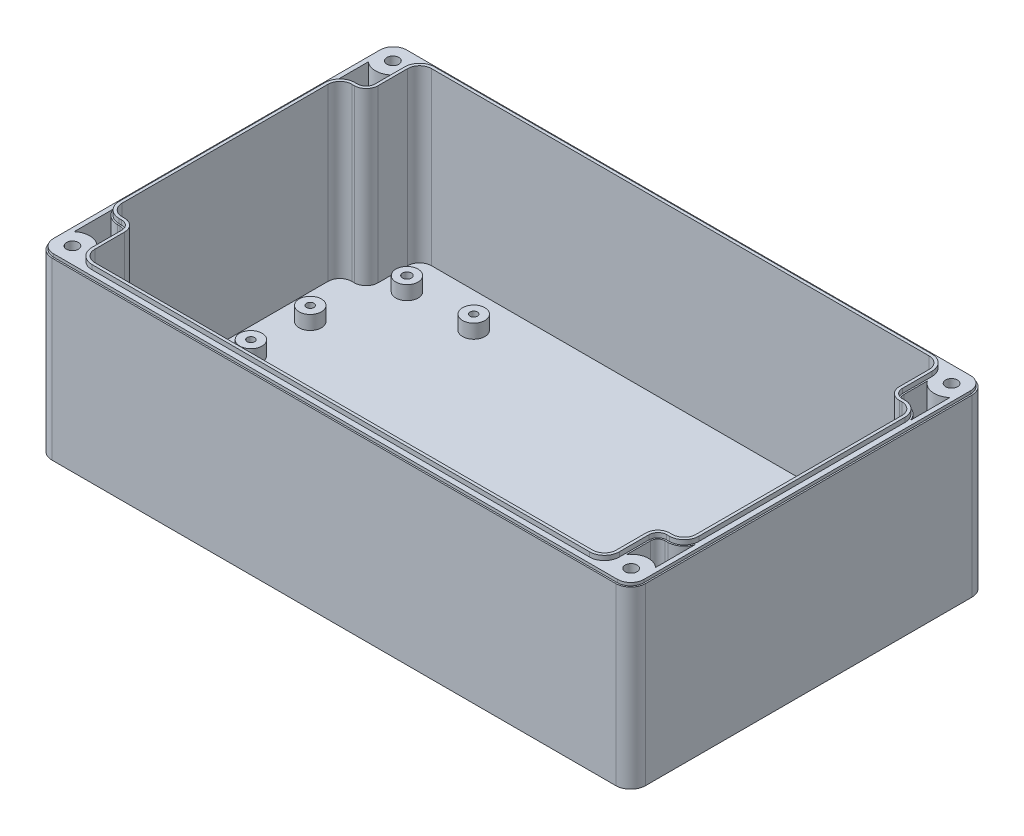
SolidWorks part; units mm, degrees
ref_plane "Front Plane" through (0, 0, 0) normal (0, 0, 1) x (1, 0, 0)
ref_plane "Top Plane" through (0, 0, 0) normal (0, 1, 0) x (1, 0, 0)
ref_plane "Right Plane" through (0, 0, 0) normal (1, 0, 0) x (0, 0, -1)
sketch "Sketch1" plane through (0, 0, 0) normal (0, 1, 0) x (1, 0, 0)
  line L1 (-100, 60) -> (100, 60)
  line L2 (-100, 60) -> (-100, -60)
  line L3 (-100, -60) -> (100, -60)
  line L4 (100, 60) -> (100, -60)
  line L5 (-100, 60) -> (100, -60) construction
  line L6 (-100, -60) -> (100, 60) construction
  point P0 (0, 0)
  dimension "D1" = 200
  dimension "D2" = 120
extrude "Boss-Extrude1" add sketch "Sketch1" along normal blind 60
fillet "Fillet1" radius 5 4 edges at (-100, 30, -60) (100, 30, -60) (100, 30, 60) (-100, 30, 60)
sketch "Sketch2" plane through (0, 60, 0) normal (0, 1, 0) x (1, 0, 0)
  line L0 (0, 60) -> (0, -60) construction
  line L1 (96.7, 56.7) -> (-96.7, 56.7)
  line L2 (96.7, 56.7) -> (96.7, -56.7)
  line L3 (96.7, -56.7) -> (-96.7, -56.7)
  line L4 (-96.7, 56.7) -> (-96.7, -56.7)
  line L5 (96.7, 56.7) -> (-96.7, -56.7) construction
  line L6 (96.7, -56.7) -> (-96.7, 56.7) construction
  line L7 (95, 60) -> (-95, 60) construction
  line L8 (-95, -60) -> (95, -60) construction
  line L9 (-100, 0) -> (99.9439, 0) construction
  line L10 (-100, 55) -> (-100, -55) construction
  line L12 (87.85, -56.7) -> (-87.85, -56.7)
  line L13 (87.85, -56.7) -> (87.85, 56.7)
  line L14 (87.85, 56.7) -> (-87.85, 56.7)
  line L15 (-87.85, -56.7) -> (-87.85, 56.7)
  line L16 (87.85, -56.7) -> (-87.85, 56.7) construction
  line L17 (87.85, 56.7) -> (-87.85, -56.7) construction
  line L18 (96.7, -38.7) -> (-96.7, -38.7)
  line L19 (96.7, -38.7) -> (96.7, 38.7)
  line L20 (96.7, 38.7) -> (-96.7, 38.7)
  line L21 (-96.7, -38.7) -> (-96.7, 38.7)
  line L22 (96.7, -38.7) -> (-96.7, 38.7) construction
  line L23 (96.7, 38.7) -> (-96.7, -38.7) construction
  circle A0 centre (-94.15, 54) radius 2
  circle A2 centre (94.15, 54) radius 2
  circle A3 centre (94.15, -54) radius 2
  circle A4 centre (-94.15, -54) radius 2
  point P0 (0, 0)
  point P18 (0, 0)
  point P19 (0, 0)
  point P30 (0, 0)
  dimension "D5" = 4
  dimension "D1" = 193.4
  dimension "D2" = 113.4
  dimension "D3" = 188.3
  dimension "D4" = 108
  dimension "D6" = 175.7
  dimension "D7" = 77.4
extrude "Cut-Extrude1" cut sketch "Sketch2" against normal offset from surface (56 mm away) 4 contours L20 L13 L1 L15 | L13 L20 L15 L18 | L13 L18 L15 L3 | L15 L20 L4 L18 | L2 L20 L13 L18 | A0 | A4 | A2 | A3 region at (0, 60, -47.7) region at (92.275, 60, 0) region at (0, 60, 0) region at (-92.275, 60, 0) region at (0, 60, 47.7) up to face at (0, 0, 0)
fillet "Fillet2" radius 4 12 edges at (87.85, 32, -56.7) (87.85, 32, -38.7) (96.7, 32, -38.7) (96.7, 32, 38.7) (87.85, 32, 38.7) (87.85, 32, 56.7) (-87.85, 32, 56.7) (-87.85, 32, 38.7) (-96.7, 32, 38.7) (-96.7, 32, -38.7) (-87.85, 32, -56.7) (-87.85, 32, -38.7)
sketch "Sketch3" plane through (0, 60, 0) normal (0, 1, 0) x (1, 0, 0)
  line L1 (83.85, 57.7) -> (-83.85, 57.7)
  line L2 (-88.85, 52.7) -> (-88.85, 42.7)
  line L3 (-91.85, 39.7) -> (-92.7, 39.7)
  line L4 (-97.7, 34.7) -> (-97.7, -34.7)
  line L5 (-92.7, -39.7) -> (-91.85, -39.7)
  line L6 (-88.85, -42.7) -> (-88.85, -52.7)
  line L7 (-83.85, -57.7) -> (83.85, -57.7)
  line L8 (88.85, -52.7) -> (88.85, -42.7)
  line L9 (91.85, -39.7) -> (92.7, -39.7)
  line L10 (97.7, -34.7) -> (97.7, 34.7)
  line L11 (92.7, 39.7) -> (91.85, 39.7)
  line L12 (88.85, 42.7) -> (88.85, 52.7)
  line L13 (87.85, 42.7) -> (87.85, 52.7)
  line L14 (92.7, 38.7) -> (91.85, 38.7)
  line L15 (96.7, -34.7) -> (96.7, 34.7)
  line L16 (91.85, -38.7) -> (92.7, -38.7)
  line L17 (87.85, -52.7) -> (87.85, -42.7)
  line L18 (-83.85, -56.7) -> (83.85, -56.7)
  line L19 (-87.85, -42.7) -> (-87.85, -52.7)
  line L20 (-92.7, -38.7) -> (-91.85, -38.7)
  line L21 (-96.7, 34.7) -> (-96.7, -34.7)
  line L22 (-91.85, 38.7) -> (-92.7, 38.7)
  line L23 (-87.85, 52.7) -> (-87.85, 42.7)
  line L24 (83.85, 56.7) -> (-83.85, 56.7)
  line L25 (87.85, 42.7) -> (87.85, 52.7)
  line L26 (92.7, 38.7) -> (91.85, 38.7)
  line L27 (96.7, -34.7) -> (96.7, 34.7)
  line L28 (91.85, -38.7) -> (92.7, -38.7)
  line L29 (87.85, -52.7) -> (87.85, -42.7)
  line L30 (-83.85, -56.7) -> (83.85, -56.7)
  line L31 (-87.85, -42.7) -> (-87.85, -52.7)
  line L32 (-92.7, -38.7) -> (-91.85, -38.7)
  line L33 (-96.7, 34.7) -> (-96.7, -34.7)
  line L34 (-91.85, 38.7) -> (-92.7, 38.7)
  line L35 (-87.85, 52.7) -> (-87.85, 42.7)
  line L36 (83.85, 56.7) -> (-83.85, 56.7)
  arc A0 (-83.85, 57.7) -> (-88.85, 52.7) centre (-83.85, 52.7) ccw
  arc A1 (-91.85, 39.7) -> (-88.85, 42.7) centre (-91.85, 42.7) ccw
  arc A2 (-92.7, 39.7) -> (-97.7, 34.7) centre (-92.7, 34.7) ccw
  arc A3 (-97.7, -34.7) -> (-92.7, -39.7) centre (-92.7, -34.7) ccw
  arc A4 (-88.85, -42.7) -> (-91.85, -39.7) centre (-91.85, -42.7) ccw
  arc A5 (-88.85, -52.7) -> (-83.85, -57.7) centre (-83.85, -52.7) ccw
  arc A6 (83.85, -57.7) -> (88.85, -52.7) centre (83.85, -52.7) ccw
  arc A7 (91.85, -39.7) -> (88.85, -42.7) centre (91.85, -42.7) ccw
  arc A8 (92.7, -39.7) -> (97.7, -34.7) centre (92.7, -34.7) ccw
  arc A9 (97.7, 34.7) -> (92.7, 39.7) centre (92.7, 34.7) ccw
  arc A10 (88.85, 42.7) -> (91.85, 39.7) centre (91.85, 42.7) ccw
  arc A11 (88.85, 52.7) -> (83.85, 57.7) centre (83.85, 52.7) ccw
  arc A12 (87.85, 42.7) -> (91.85, 38.7) centre (91.85, 42.7) ccw
  arc A13 (96.7, 34.7) -> (92.7, 38.7) centre (92.7, 34.7) ccw
  arc A14 (92.7, -38.7) -> (96.7, -34.7) centre (92.7, -34.7) ccw
  arc A15 (91.85, -38.7) -> (87.85, -42.7) centre (91.85, -42.7) ccw
  arc A16 (83.85, -56.7) -> (87.85, -52.7) centre (83.85, -52.7) ccw
  arc A17 (-87.85, -52.7) -> (-83.85, -56.7) centre (-83.85, -52.7) ccw
  arc A18 (-87.85, -42.7) -> (-91.85, -38.7) centre (-91.85, -42.7) ccw
  arc A19 (-96.7, -34.7) -> (-92.7, -38.7) centre (-92.7, -34.7) ccw
  arc A20 (-92.7, 38.7) -> (-96.7, 34.7) centre (-92.7, 34.7) ccw
  arc A21 (-91.85, 38.7) -> (-87.85, 42.7) centre (-91.85, 42.7) ccw
  arc A22 (-83.85, 56.7) -> (-87.85, 52.7) centre (-83.85, 52.7) ccw
  arc A23 (87.85, 52.7) -> (83.85, 56.7) centre (83.85, 52.7) ccw
  arc A24 (87.85, 42.7) -> (91.85, 38.7) centre (91.85, 42.7) ccw
  arc A25 (96.7, 34.7) -> (92.7, 38.7) centre (92.7, 34.7) ccw
  arc A26 (92.7, -38.7) -> (96.7, -34.7) centre (92.7, -34.7) ccw
  arc A27 (91.85, -38.7) -> (87.85, -42.7) centre (91.85, -42.7) ccw
  arc A28 (83.85, -56.7) -> (87.85, -52.7) centre (83.85, -52.7) ccw
  arc A29 (-87.85, -52.7) -> (-83.85, -56.7) centre (-83.85, -52.7) ccw
  arc A30 (-87.85, -42.7) -> (-91.85, -38.7) centre (-91.85, -42.7) ccw
  arc A31 (-96.7, -34.7) -> (-92.7, -38.7) centre (-92.7, -34.7) ccw
  arc A32 (-92.7, 38.7) -> (-96.7, 34.7) centre (-92.7, 34.7) ccw
  arc A33 (-91.85, 38.7) -> (-87.85, 42.7) centre (-91.85, 42.7) ccw
  arc A34 (-83.85, 56.7) -> (-87.85, 52.7) centre (-83.85, 52.7) ccw
  arc A35 (87.85, 52.7) -> (83.85, 56.7) centre (83.85, 52.7) ccw
  dimension "D1" = 0
  dimension "D2" = 1
extrude "Boss-Extrude2" add sketch "Sketch3" along normal blind 1.55
sketch "Sketch4" plane through (0, 4, 0) normal (0, 1, 0) x (1, 0, 0)
  circle A1 centre (-94.15, 54) radius 2
  circle A2 centre (-94.15, 54) radius 2
  circle A3 centre (94.15, 54) radius 2
  circle A4 centre (94.15, 54) radius 2
  circle A5 centre (-94.15, -54) radius 2
  circle A6 centre (-94.15, -54) radius 2
  circle A7 centre (94.15, -54) radius 2
  circle A8 centre (94.15, -54) radius 2
  dimension "D1" = 0
  dimension "D2" = 0
  dimension "D3" = 0
  dimension "D4" = 0
extrude "Cut-Extrude2" cut sketch "Sketch4" against normal up to next
sketch "Sketch5" plane through (0, 0, 0) normal (0, -1, 0) x (1, 0, 0)
  circle A0 centre (-94.15, 54) radius 3.45
  circle A1 centre (94.15, 54) radius 3.45
  circle A2 centre (94.15, -54) radius 3.45
  circle A3 centre (-94.15, -54) radius 3.45
  dimension "D1" = 6.9
extrude "Cut-Extrude3" cut sketch "Sketch5" against normal blind 52
sketch "Sketch6" plane through (0, 60, 0) normal (0, 1, 0) x (1, 0, 0)
  line L8 (95, 58) -> (-95, 58)
  line L9 (-98, 55) -> (-98, -55)
  line L10 (-95, -58) -> (95, -58)
  line L11 (98, -55) -> (98, 55)
  line L12 (95, 58) -> (-95, 58)
  line L13 (-98, 55) -> (-98, -55)
  line L14 (-95, -58) -> (95, -58)
  line L15 (98, -55) -> (98, 55)
  line L25 (-100, 55) -> (-100, -55) construction
  line L37 (83.85, 58.2) -> (-83.85, 58.2)
  line L38 (89.35, 42.7) -> (89.35, 52.7)
  line L39 (92.7, 40.2) -> (91.85, 40.2)
  line L40 (98.2, -34.7) -> (98.2, 34.7)
  line L41 (91.85, -40.2) -> (92.7, -40.2)
  line L42 (89.35, -52.7) -> (89.35, -42.7)
  line L43 (-83.85, -58.2) -> (83.85, -58.2)
  line L44 (-89.35, -42.7) -> (-89.35, -52.7)
  line L45 (-92.7, -40.2) -> (-91.85, -40.2)
  line L46 (-98.2, 34.7) -> (-98.2, -34.7)
  line L47 (-91.85, 40.2) -> (-92.7, 40.2)
  line L48 (-89.35, 52.7) -> (-89.35, 42.7)
  line L49 (83.85, 58.2) -> (-83.85, 58.2)
  line L50 (89.35, 42.7) -> (89.35, 52.7)
  line L51 (92.7, 40.2) -> (91.85, 40.2)
  line L52 (98.2, -34.7) -> (98.2, 34.7)
  line L53 (91.85, -40.2) -> (92.7, -40.2)
  line L54 (89.35, -52.7) -> (89.35, -42.7)
  line L55 (-83.85, -58.2) -> (83.85, -58.2)
  line L56 (-89.35, -42.7) -> (-89.35, -52.7)
  line L57 (-92.7, -40.2) -> (-91.85, -40.2)
  line L58 (-98.2, 34.7) -> (-98.2, -34.7)
  line L59 (-91.85, 40.2) -> (-92.7, 40.2)
  line L60 (-89.35, 52.7) -> (-89.35, 42.7)
  arc A8 (-95, 58) -> (-98, 55) centre (-95, 55) ccw
  arc A9 (-98, -55) -> (-95, -58) centre (-95, -55) ccw
  arc A10 (95, -58) -> (98, -55) centre (95, -55) ccw
  arc A11 (98, 55) -> (95, 58) centre (95, 55) ccw
  arc A12 (-95, 58) -> (-98, 55) centre (-95, 55) ccw
  arc A13 (-98, -55) -> (-95, -58) centre (-95, -55) ccw
  arc A14 (95, -58) -> (98, -55) centre (95, -55) ccw
  arc A15 (98, 55) -> (95, 58) centre (95, 55) ccw
  circle A24 centre (-94.15, 54) radius 5.85
  circle A25 centre (94.15, 54) radius 5.85
  circle A26 centre (94.15, -54) radius 5.85
  circle A27 centre (-94.15, -54) radius 5.85
  arc A36 (89.35, 52.7) -> (83.85, 58.2) centre (83.85, 52.7) ccw
  arc A37 (89.35, 42.7) -> (91.85, 40.2) centre (91.85, 42.7) ccw
  arc A38 (98.2, 34.7) -> (92.7, 40.2) centre (92.7, 34.7) ccw
  arc A39 (92.7, -40.2) -> (98.2, -34.7) centre (92.7, -34.7) ccw
  arc A40 (91.85, -40.2) -> (89.35, -42.7) centre (91.85, -42.7) ccw
  arc A41 (83.85, -58.2) -> (89.35, -52.7) centre (83.85, -52.7) ccw
  arc A42 (-89.35, -52.7) -> (-83.85, -58.2) centre (-83.85, -52.7) ccw
  arc A43 (-89.35, -42.7) -> (-91.85, -40.2) centre (-91.85, -42.7) ccw
  arc A44 (-98.2, -34.7) -> (-92.7, -40.2) centre (-92.7, -34.7) ccw
  arc A45 (-92.7, 40.2) -> (-98.2, 34.7) centre (-92.7, 34.7) ccw
  arc A46 (-91.85, 40.2) -> (-89.35, 42.7) centre (-91.85, 42.7) ccw
  arc A47 (-83.85, 58.2) -> (-89.35, 52.7) centre (-83.85, 52.7) ccw
  arc A48 (89.35, 52.7) -> (83.85, 58.2) centre (83.85, 52.7) ccw
  arc A49 (89.35, 42.7) -> (91.85, 40.2) centre (91.85, 42.7) ccw
  arc A50 (98.2, 34.7) -> (92.7, 40.2) centre (92.7, 34.7) ccw
  arc A51 (92.7, -40.2) -> (98.2, -34.7) centre (92.7, -34.7) ccw
  arc A52 (91.85, -40.2) -> (89.35, -42.7) centre (91.85, -42.7) ccw
  arc A53 (83.85, -58.2) -> (89.35, -52.7) centre (83.85, -52.7) ccw
  arc A54 (-89.35, -52.7) -> (-83.85, -58.2) centre (-83.85, -52.7) ccw
  arc A55 (-89.35, -42.7) -> (-91.85, -40.2) centre (-91.85, -42.7) ccw
  arc A56 (-98.2, -34.7) -> (-92.7, -40.2) centre (-92.7, -34.7) ccw
  arc A57 (-92.7, 40.2) -> (-98.2, 34.7) centre (-92.7, 34.7) ccw
  arc A58 (-91.85, 40.2) -> (-89.35, 42.7) centre (-91.85, 42.7) ccw
  arc A59 (-83.85, 58.2) -> (-89.35, 52.7) centre (-83.85, 52.7) ccw
  dimension "D1" = 2
  dimension "D2" = 0.5
extrude "Cut-Extrude4" cut sketch "Sketch6" against normal up to surface (56 mm away) contours L59 A58 L60 A24 L13 A57 | A50 L15 A25 L50 A49 L51 | L53 A52 L54 A26 L15 A51 | A56 L13 A27 L56 A55 L57 region at (93.8916, 60, -44.1874) region at (93.8916, 60, 44.1874) region at (-93.8916, 60, -44.1874) region at (-93.8916, 60, 44.1874) up to face at (0, 4, 0)
sketch "Sketch7" plane through (0, 0, 0) normal (0, -1, 0) x (1, 0, 0)
  line L0 (-94.15, 54) -> (-94.15, -54) construction
  line L1 (94.15, -45) -> (-94.15, -45)
  line L2 (94.15, -45) -> (94.15, 45)
  line L3 (94.15, 45) -> (-94.15, 45)
  line L4 (-94.15, -45) -> (-94.15, 45)
  line L5 (94.15, -45) -> (-94.15, 45) construction
  line L6 (94.15, 45) -> (-94.15, -45) construction
  circle A0 centre (-94.15, 45) radius 2.225
  circle A1 centre (94.15, 45) radius 2.225
  circle A2 centre (94.15, -45) radius 2.225
  circle A3 centre (-94.15, -45) radius 2.225
  point P0 (0, 0)
  dimension "D2" = 4.45
  dimension "D1" = 90
extrude "Cut-Extrude5" cut sketch "Sketch7" against normal up to next contours A0 | A1 | A2 | A3
sketch "Sketch8" plane through (0, 4, 0) normal (0, 1, 0) x (1, 0, 0)
  line L0 (0, 60) -> (0, -60) construction
  line L1 (95, 60) -> (-95, 60) construction
  line L2 (-95, -60) -> (95, -60) construction
  line L3 (-100, 0) -> (100, 0) construction
  line L4 (-100, 55) -> (-100, -55) construction
  line L5 (100, -55) -> (100, 55) construction
  line L6 (-80.4, 45) -> (80.4, 45) construction
  line L7 (-80.4, 45) -> (-80.4, -45) construction
  line L8 (-88, 60) -> (-88, -60) construction
  circle A0 centre (-80.4, 45) radius 3.75
  circle A1 centre (-80.4, 45) radius 1.5
  circle A2 centre (80.4, 45) radius 3.75
  circle A3 centre (80.4, 45) radius 1.5
  circle A4 centre (80.4, -45) radius 3.75
  circle A5 centre (80.4, -45) radius 1.5
  circle A6 centre (-80.4, -45) radius 3.75
  circle A7 centre (-80.4, -45) radius 1.5
  circle A8 centre (-57.9, 45) radius 3.75
  circle A9 centre (-57.9, 45) radius 1.25
  circle A12 centre (-57.9, -45) radius 1.25
  circle A13 centre (-57.9, -45) radius 3.75
  circle A16 centre (-88, 0) radius 3.75
  circle A17 centre (-88, 0) radius 1.25
  circle A18 centre (-88, 20) radius 3.75
  circle A19 centre (-88, 20) radius 1.25
  circle A20 centre (-88, -20) radius 1.25
  circle A21 centre (-88, -20) radius 3.75
  circle A22 centre (88, -20) radius 3.75
  circle A23 centre (88, -20) radius 1.25
  circle A24 centre (88, 0) radius 1.25
  circle A25 centre (88, 0) radius 3.75
  circle A26 centre (88, 20) radius 3.75
  circle A27 centre (88, 20) radius 1.25
  dimension "D1" = 7.5
  dimension "D2" = 3
  dimension "D5" = 2.5
  dimension "D3" = 160.8
  dimension "D4" = 90
  dimension "D6" = 22.5
  dimension "D7" = 176
  dimension "D8" = 40
extrude "Boss-Extrude3" add sketch "Sketch8" along normal blind 4.7
sketch "Sketch9" plane through (0, 60, 0) normal (0, 1, 0) x (1, 0, 0)
  line L0 (95, 59.5) -> (-95, 59.5)
  line L1 (-99.5, 55) -> (-99.5, -55)
  line L2 (-95, -59.5) -> (95, -59.5)
  line L3 (99.5, -55) -> (99.5, 55)
  line L4 (95, 60) -> (-95, 60)
  line L5 (-100, 55) -> (-100, -55)
  line L6 (-95, -60) -> (95, -60)
  line L7 (100, -55) -> (100, 55)
  line L8 (95, 60) -> (-95, 60)
  line L9 (-100, 55) -> (-100, -55)
  line L10 (-95, -60) -> (95, -60)
  line L11 (100, -55) -> (100, 55)
  arc A0 (-95, 59.5) -> (-99.5, 55) centre (-95, 55) ccw
  arc A1 (-99.5, -55) -> (-95, -59.5) centre (-95, -55) ccw
  arc A2 (95, -59.5) -> (99.5, -55) centre (95, -55) ccw
  arc A3 (99.5, 55) -> (95, 59.5) centre (95, 55) ccw
  arc A4 (-95, 60) -> (-100, 55) centre (-95, 55) ccw
  arc A5 (-100, -55) -> (-95, -60) centre (-95, -55) ccw
  arc A6 (95, -60) -> (100, -55) centre (95, -55) ccw
  arc A7 (100, 55) -> (95, 60) centre (95, 55) ccw
  arc A8 (-95, 60) -> (-100, 55) centre (-95, 55) ccw
  arc A9 (-100, -55) -> (-95, -60) centre (-95, -55) ccw
  arc A10 (95, -60) -> (100, -55) centre (95, -55) ccw
  arc A11 (100, 55) -> (95, 60) centre (95, 55) ccw
  dimension "D1" = 0
  dimension "D2" = 0.5
extrude "Cut-Extrude6" cut sketch "Sketch9" against normal blind 1
